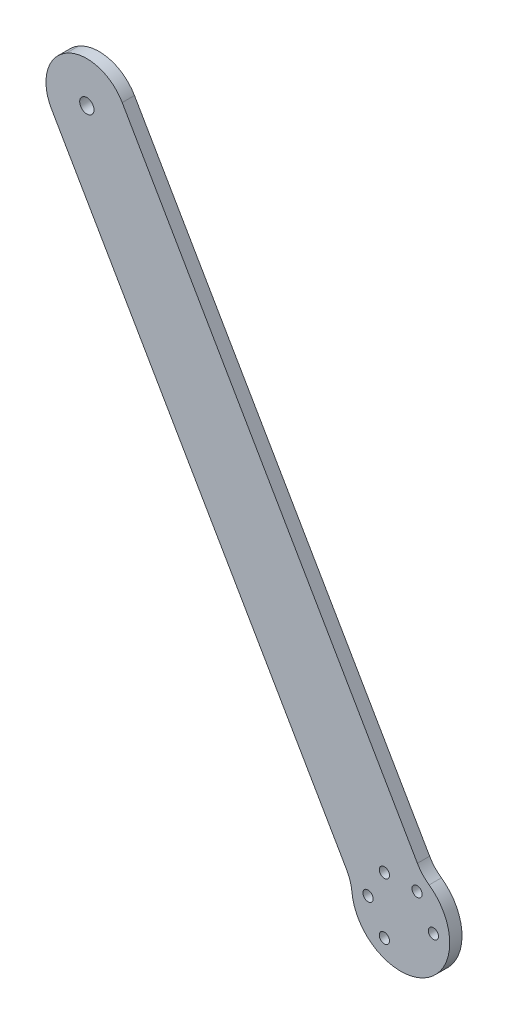
SolidWorks part; units mm, degrees
ref_plane "Front Plane" through (0, 0, 0) normal (0, 0, 1) x (1, 0, 0)
ref_plane "Top Plane" through (0, 0, 0) normal (0, 1, 0) x (1, 0, 0)
ref_plane "Right Plane" through (0, 0, 0) normal (1, 0, 0) x (0, 0, -1)
sketch "Sketch1" plane through (0, 0, 0) normal (0, 0, 1) x (1, 0, 0)
  line L0 (-11.9769, 0.7446) -> (-90.4769, 136.7106)
  line L1 (-90.4769, 136.7106) -> (-73.1564, 146.7106)
  line L2 (-73.1564, 146.7106) -> (5.3436, 10.7446)
  line L3 (-8, 0) -> (-4, -6.9282) construction
  line L4 (-81.8166, 141.7106) -> (-6, 10.3923) construction
  circle A0 centre (0, 0) radius 12
  circle A1 centre (8, 0) radius 1.25 construction
  circle A2 centre (4, 6.9282) radius 1.25 construction
  circle A3 centre (-4, 6.9282) radius 1.25 construction
  circle A4 centre (-8, 0) radius 1.25 construction
  circle A5 centre (-4, -6.9282) radius 1.25 construction
  circle A6 centre (8, 0) radius 1.25
  circle A7 centre (4, 6.9282) radius 1.25
  circle A8 centre (-4, 6.9282) radius 1.25
  circle A9 centre (-8, 0) radius 1.25
  circle A10 centre (-4, -6.9282) radius 1.25
  circle A12 centre (-76.8166, 133.0503) radius 1.75
  point P23 (-81.8166, 141.7106)
  dimension "D1" = 24
  dimension "D5" = 3.5
  dimension "D2" = 20
  dimension "D3" = 157
  dimension "D4" = 10
  dimension "D6" = 10
extrude "Boss-Extrude1" add sketch "Sketch1" along normal blind 3 contours A0 L2 L1 L0 | A0 A9 A10 A8 A7 A6 region at (-43.402, 75.1745, 0) region at (0.0459, -0.0795, 0)
fillet "Fillet1" radius 10 4 edges at (-11.9769, 0.7446, 1.5) (5.3436, 10.7446, 1.5) (-90.4769, 136.7106, 1.5) (-73.1564, 146.7106, 1.5)
